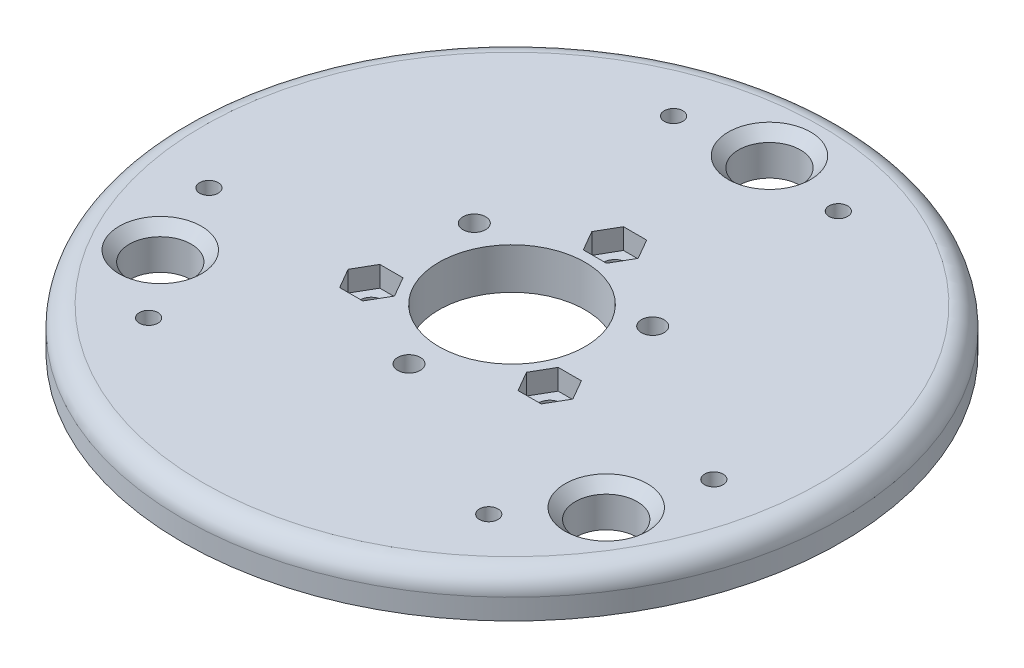
SolidWorks part; units mm, degrees
ref_plane "Спереди" through (0, 0, 0) normal (0, 0, 1) x (1, 0, 0)
ref_plane "Сверху" through (0, 0, 0) normal (0, 1, 0) x (1, 0, 0)
ref_plane "Справа" through (0, 0, 0) normal (1, 0, 0) x (0, 0, -1)
sketch "Эскиз1" plane through (0, 0, 0) normal (0, 1, 0) x (1, 0, 0)
  circle A3 centre (0, 0) radius 32
  circle A4 centre (0, 0) radius 7.1
  circle A6 centre (0, 0) radius 25 construction
  circle A7 centre (0, 25) radius 3
  circle A8 centre (21.6506, -12.5) radius 3
  circle A9 centre (-21.6506, -12.5) radius 3
  dimension "D4" = 64
  dimension "D1" = 14.2
  dimension "D2" = 50
  dimension "D3" = 6
  dimension "D5" = 3
extrude "Бобышка-Вытянуть1" add sketch "Эскиз1" along normal blind 4
fillet "Скругление1" radius 2 1 edges at (0, 4, 32)
sketch "Эскиз2" plane through (0, 4, 0) normal (0, 1, 0) x (1, 0, 0)
  circle A0 centre (0, 0) radius 10 construction
  circle A1 centre (0, 10) radius 1.1
  circle A2 centre (8.6603, 5) radius 1.1
  circle A3 centre (8.6603, -5) radius 1.1
  circle A4 centre (0, -10) radius 1.1
  circle A5 centre (-8.6603, -5) radius 1.1
  circle A6 centre (-8.6603, 5) radius 1.1
  dimension "D3" = 6
  dimension "D1" = 20
  dimension "D2" = 2.2
extrude "Вырез-Вытянуть1" cut sketch "Эскиз2" against normal through all
sketch "Эскиз3" plane through (0, 4, 0) normal (0, 1, 0) x (1, 0, 0)
  line L0 (9.7861, -6.95) -> (10.9119, -5)
  line L1 (1.1258, 8.05) -> (2.2517, 10)
  line L2 (2.2517, 10) -> (1.1258, 11.95)
  line L3 (1.1258, 11.95) -> (-1.1258, 11.95)
  line L4 (-1.1258, 11.95) -> (-2.2517, 10)
  line L5 (-2.2517, 10) -> (-1.1258, 8.05)
  line L6 (-1.1258, 8.05) -> (1.1258, 8.05)
  line L7 (10.9119, -5) -> (9.7861, -3.05)
  line L8 (9.7861, -3.05) -> (7.5344, -3.05)
  line L9 (7.5344, -3.05) -> (6.4086, -5)
  line L10 (6.4086, -5) -> (7.5344, -6.95)
  line L11 (7.5344, -6.95) -> (9.7861, -6.95)
  line L12 (-10.9119, -5) -> (-9.7861, -6.95)
  line L13 (-9.7861, -6.95) -> (-7.5344, -6.95)
  line L14 (-7.5344, -6.95) -> (-6.4086, -5)
  line L15 (-6.4086, -5) -> (-7.5344, -3.05)
  line L16 (-7.5344, -3.05) -> (-9.7861, -3.05)
  line L17 (-9.7861, -3.05) -> (-10.9119, -5)
  circle A0 centre (0, 10) radius 1.95 construction
  circle A1 centre (8.6603, -5) radius 1.95 construction
  circle A2 centre (-8.6603, -5) radius 1.95 construction
  circle A3 centre (-8.6603, -5) radius 1.1 construction
  point P1 (0, 8.05)
  dimension "D1" = 3.9
  dimension "D2" = 3
extrude "Вырез-Вытянуть2" cut sketch "Эскиз3" against normal blind 2
sketch "Эскиз4" plane through (0, 0, 0) normal (0, -1, 0) x (1, 0, 0)
  line L0 (7.5344, -6.95) -> (9.7861, -6.95)
  line L1 (-1.1258, 8.05) -> (1.1258, 8.05)
  line L2 (1.1258, 8.05) -> (2.2517, 10)
  line L3 (2.2517, 10) -> (1.1258, 11.95)
  line L4 (1.1258, 11.95) -> (-1.1258, 11.95)
  line L5 (-1.1258, 11.95) -> (-2.2517, 10)
  line L6 (-2.2517, 10) -> (-1.1258, 8.05)
  line L7 (9.7861, -6.95) -> (10.9119, -5)
  line L8 (10.9119, -5) -> (9.7861, -3.05)
  line L9 (9.7861, -3.05) -> (7.5344, -3.05)
  line L10 (7.5344, -3.05) -> (6.4086, -5)
  line L11 (6.4086, -5) -> (7.5344, -6.95)
  line L12 (-9.7861, -3.05) -> (-10.9119, -5)
  line L13 (-10.9119, -5) -> (-9.7861, -6.95)
  line L14 (-9.7861, -6.95) -> (-7.5344, -6.95)
  line L15 (-7.5344, -6.95) -> (-6.4086, -5)
  line L16 (-6.4086, -5) -> (-7.5344, -3.05)
  line L17 (-7.5344, -3.05) -> (-9.7861, -3.05)
  circle A0 centre (0, 10) radius 1.95 construction
  circle A1 centre (8.6603, -5) radius 1.95 construction
  circle A2 centre (-8.6603, -5) radius 1.95 construction
  circle A3 centre (8.6603, -5) radius 1.1 construction
  dimension "D1" = 3.9
  dimension "D2" = 3
extrude "Вырез-Вытянуть3" cut sketch "Эскиз4" against normal blind 2
chamfer "Фаска1" distance 1 angle 45 3 edges at (0, 4, -22) (-21.6506, 4, 15.5) (21.6506, 4, 15.5)
sketch "Эскиз5" plane through (0, 4, 0) normal (0, 1, 0) x (1, 0, 0)
  line L0 (0, 0) -> (0, 25) construction
  line L1 (-8, 23.6854) -> (8, 23.6854) construction
  circle A0 centre (0, 0) radius 25 construction
  circle A1 centre (8, 23.6854) radius 0.9
  circle A2 centre (-8, 23.6854) radius 0.9
  circle A3 centre (24.5122, -4.9145) radius 0.9
  circle A4 centre (16.5122, -18.7709) radius 0.9
  circle A5 centre (-16.5122, -18.7709) radius 0.9
  circle A6 centre (-24.5122, -4.9145) radius 0.9
  dimension "D2" = 1.8
  dimension "D3" = 1.8
  dimension "D1" = 16
extrude "Вырез-Вытянуть4" cut sketch "Эскиз5" against normal through all
equation "\"motor_diameter\"= 30"
equation "\"mm_diameter\"= IIF ( \"motor_diameter\" < 34 , 41 , \"motor_diameter\" + 8 )"
equation "\"upper_shafts_diameter\"= 5"
equation "\"upper_shats_length\"= 180"
equation "\"upper_bearing_d1\"= 10"
equation "\"upper_bearing_d2\"= 5"
equation "\"upper_bearing_h\"= 15"
equation "\"lower_shafts_diameter\"= 5"
equation "\"lower_shafts_length\"= 180"
equation "\"lower_bearing_d1\"= 10"
equation "\"lower_bearing_d2\"= 5"
equation "\"lower_bearing_h\"= 15"
equation "\"print_offset\"= 0.2"
equation "\"bh_screws_d\"= 2"
equation "\"bh_screws_h\"= 20"
equation "\"bh_screws_hh_d\"= 3.4"
equation "\"bh_screws_hh_h\"= 2"
equation "\"bh_nut_d\"= 3.8"
equation "\"bh_nut_h\"= 2"
equation "\"motor_screws_d\"= 3"
equation "\"motor_screws_h\"= 16"
equation "\"motor_screws_hh_d\"= 5.5"
equation "\"motor_screws_hh_h\"= 3"
equation "\"plate_hole_distance\"= 25.4"
equation "\"plate_screws_d\"= 6.5"
equation "\"shafts_diameter\"= IIF ( \"mm_diameter\" < 42 , 42 + 8 , \"mm_diameter\" + 8 )"
equation "\"D4@Эскиз1\"= \"system_radius\" * 2"
equation "\"central_hole_diameter\"= 8"
equation "\"bh_thikness\"= 4"
equation "\"D2@Эскиз1\"=\"shafts_diameter\""
equation "\"D3@Эскиз1\"= \"lower_shafts_diameter\" + 1"
equation "\"D1@Бобышка-Вытянуть1\"=\"bh_thikness\""
equation "\"D2@Эскиз2\"=\"bh_screws_d\"+\"print_offset\""
equation "\"D1@Эскиз3\"=\"bh_nut_d\"+\"print_offset\"/2"
equation "\"D1@Вырез-Вытянуть2\"=\"bh_nut_h\""
equation "\"D1@Эскиз4\"=\"bh_nut_d\"+\"print_offset\"/2"
equation "\"D1@Вырез-Вытянуть3\"=\"bh_nut_h\""
equation "\"D2@Эскиз5\"=\"bh_screws_d\"-\"print_offset\""
equation "\"D3@Эскиз5\"=\"D2@Эскиз5\""
equation "\"ends_screws_d\"= 4"
equation "\"ends_screws_h\"= 16"
equation "\"ends_screws_hh_d\"= 6.7"
equation "\"ends_screws_hh_h\"= 4.1"
equation "\"ends_nut_d\"= 6.8"
equation "\"ends_nut_h\"= 3"
equation "\"system_radius\" = ( \"shafts_diameter\" + 12 + \"bh_thikness\" / 2 ) / 2"
equation "\"encoder_distance\"= \"system_radius\" + 4"
equation "\"tape_position\"= \"encoder_distance\" - 2 + 3.9 + 1.7 / 2"
equation "\"D1@Эскиз1\"=\"print_offset\"+14.00мм"
equation "\"ft_sensor_d1\" = 9.8"
equation "\"ft_sensor_d2\"= 24.9"
equation "\"ft_sensor_h\"= 7"
equation "\"carbon_pipe_d\"= 14"
